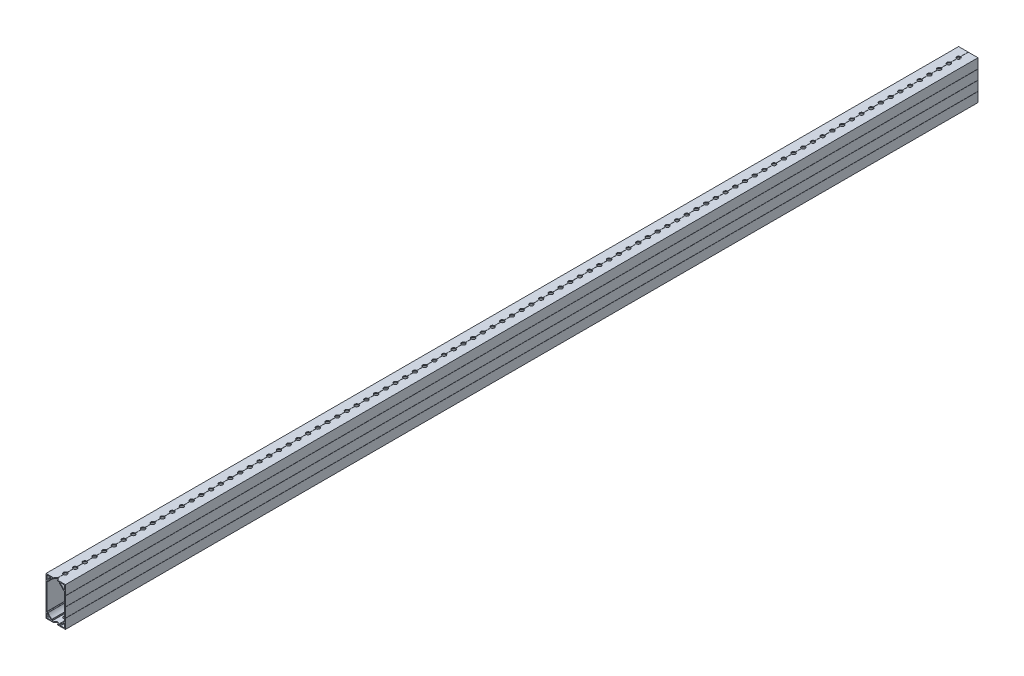
SolidWorks part; units mm, degrees
ref_plane "Front Plane" through (0, 0, 0) normal (0, 0, 1) x (1, 0, 0)
ref_plane "Top Plane" through (0, 0, 0) normal (0, 1, 0) x (1, 0, 0)
ref_plane "Right Plane" through (0, 0, 0) normal (1, 0, 0) x (0, 0, -1)
other "Configuration Table"
sketch "Sketch3" plane through (0, 0, 0) normal (0, 0, 1) x (1, 0, 0)
  line L0 (0, 12.7) -> (0, -12.7) construction
  line L1 (12.7, -25.4) -> (0.127, -25.4)
  line L2 (12.7, -12.827) -> (12.7, -25.4)
  line L3 (12.573, -12.7) -> (12.7, -12.827)
  line L4 (-10.9924, -24.384) -> (-6.5971, -24.384)
  line L5 (-11.684, -19.2971) -> (-11.684, -23.6924)
  line L6 (12.7, -12.573) -> (12.573, -12.7)
  line L7 (12.7, -0.127) -> (12.7, -12.573)
  line L10 (12.573, 0) -> (12.7, -0.127)
  line L11 (0.127, -25.4) -> (0, -25.273)
  line L14 (11.684, 0) -> (11.684, -17.5895)
  line L15 (11.684, -17.5895) -> (9.979, -17.5895)
  line L18 (4.8895, -22.679) -> (4.8895, -24.384)
  line L19 (11.684, -19.2971) -> (11.684, -23.6924)
  line L20 (10.9924, -24.384) -> (6.5971, -24.384)
  line L21 (13.97, 0) -> (-13.97, 0) construction
  line L37 (12.573, 0) -> (12.7, 0.127)
  line L46 (-4.8895, -24.384) -> (4.8895, -24.384)
  line L47 (-4.8895, -22.679) -> (-4.8895, -24.384)
  line L48 (-11.684, -17.5895) -> (-9.979, -17.5895)
  line L49 (-11.684, 0) -> (-11.684, -17.5895)
  line L57 (-0.127, 25.4) -> (-12.7, 25.4)
  line L58 (-12.7, 12.827) -> (-12.7, 25.4)
  line L59 (-12.573, 12.7) -> (-12.7, 12.827)
  line L60 (-12.7, 12.573) -> (-12.573, 12.7)
  line L61 (-12.7, 0.127) -> (-12.7, 12.573)
  line L62 (-12.573, 0) -> (-12.7, 0.127)
  line L63 (-0.127, 25.4) -> (0, 25.273)
  line L64 (-11.684, 0) -> (-11.684, 17.5895)
  line L65 (-11.684, 17.5895) -> (-9.979, 17.5895)
  line L66 (-4.8895, 22.679) -> (-4.8895, 24.384)
  line L67 (-4.8895, 24.384) -> (4.8895, 24.384)
  line L69 (10.9924, 24.384) -> (6.5971, 24.384)
  line L70 (11.684, 19.2971) -> (11.684, 23.6924)
  line L71 (4.8895, 22.679) -> (4.8895, 24.384)
  line L72 (11.684, 17.5895) -> (9.979, 17.5895)
  line L73 (11.684, 0) -> (11.684, 17.5895)
  line L74 (0.127, 25.4) -> (0, 25.273)
  line L76 (12.7, 0.127) -> (12.7, 12.573)
  line L77 (12.7, 12.573) -> (12.573, 12.7)
  line L78 (-11.684, 19.2971) -> (-11.684, 23.6924)
  line L79 (-10.9924, 24.384) -> (-6.5971, 24.384)
  line L80 (12.573, 12.7) -> (12.7, 12.827)
  line L81 (12.7, 12.827) -> (12.7, 25.4)
  line L82 (12.7, 25.4) -> (0.127, 25.4)
  line L96 (-0.127, -25.4) -> (0, -25.273)
  line L118 (-12.573, 0) -> (-12.7, -0.127)
  line L119 (-12.7, -0.127) -> (-12.7, -12.573)
  line L120 (-12.7, -12.573) -> (-12.573, -12.7)
  line L121 (-12.573, -12.7) -> (-12.7, -12.827)
  line L122 (-12.7, -12.827) -> (-12.7, -25.4)
  line L123 (-12.7, -25.4) -> (-0.127, -25.4)
  arc A0 (9.979, -17.5895) -> (4.8895, -22.679) centre (0, -12.7) cw
  arc A1 (6.5971, -24.384) -> (6.2412, -23.0994) centre (6.5971, -23.6924) cw
  arc A2 (10.3994, -18.9412) -> (6.2412, -23.0994) centre (0, -12.7) cw
  arc A3 (10.3994, -18.9412) -> (11.684, -19.2971) centre (10.9924, -19.2971) cw
  arc A4 (11.684, -23.6924) -> (10.9924, -24.384) centre (10.9924, -23.6924) cw
  arc A10 (-11.684, -23.6924) -> (-10.9924, -24.384) centre (-10.9924, -23.6924) ccw
  arc A11 (-10.3994, -18.9412) -> (-11.684, -19.2971) centre (-10.9924, -19.2971) ccw
  arc A12 (-10.3994, -18.9412) -> (-6.2412, -23.0994) centre (0, -12.7) ccw
  arc A14 (-6.5971, -24.384) -> (-6.2412, -23.0994) centre (-6.5971, -23.6924) ccw
  arc A24 (-9.979, 17.5895) -> (-4.8895, 22.679) centre (0, 12.7) cw
  arc A25 (-6.5971, 24.384) -> (-6.2412, 23.0994) centre (-6.5971, 23.6924) cw
  arc A30 (-10.3994, 18.9412) -> (-6.2412, 23.0994) centre (0, 12.7) cw
  arc A31 (-10.3994, 18.9412) -> (-11.684, 19.2971) centre (-10.9924, 19.2971) cw
  arc A32 (-11.684, 23.6924) -> (-10.9924, 24.384) centre (-10.9924, 23.6924) cw
  arc A33 (11.684, 23.6924) -> (10.9924, 24.384) centre (10.9924, 23.6924) ccw
  arc A34 (10.3994, 18.9412) -> (11.684, 19.2971) centre (10.9924, 19.2971) ccw
  arc A35 (10.3994, 18.9412) -> (6.2412, 23.0994) centre (0, 12.7) ccw
  arc A41 (6.5971, 24.384) -> (6.2412, 23.0994) centre (6.5971, 23.6924) ccw
  arc A42 (9.979, 17.5895) -> (4.8895, 22.679) centre (0, 12.7) ccw
  arc A46 (-9.979, -17.5895) -> (-4.8895, -22.679) centre (0, -12.7) ccw
  point P71 (0, -24.384)
  point P104 (-11.684, -8.7948)
  point P108 (11.684, -8.7948)
  point P130 (11.684, 8.7948)
  point P131 (-11.684, 8.7948)
  point P132 (0, 24.384)
  dimension "D4" = 0.6916
  dimension "D7" = 11.1125
  dimension "D14" = 12.1285
  dimension "D1" = 25.4
  dimension "D2" = 12.573
  dimension "D3" = 5.7785
  dimension "D5" = 12.7
  dimension "D6" = 4.8895
  dimension "D8" = 1.016
  dimension "D9" = 135
  dimension "D10" = 0.127
  dimension "D11" = 1.016
  dimension "D12" = 135
  dimension "D13" = 135
extrude "Boss-Extrude1" add sketch "Sketch3" along normal blind 1193.8 contours L48 A46 L47 L46 L18 A0 L15 L14 L73 L72 A42 L71 L67 L66 A24 L65 L64 L49 | A32 L78 A31 A30 A25 L79 | L69 A41 A35 A34 L70 A33 | L4 A14 A12 A11 L5 A10 | A4 L19 A3 A2 A1 L20 | L57 L58 L59 L60 L61 L62 L118 L119 L120 L121 L122 L123 L96 L11 L1 L2 L3 L6 L7 L10 L37 L76 L77 L80 L81 L82 L74 L63 region at (-9.5535, -22.2535, 0) region at (0, 0, 0) region at (9.5535, -22.2535, 0) region at (9.5535, 22.2535, 0) region at (-9.5535, 22.2535, 0)
sketch "Sketch2" plane through (25.4, 25.4, 0) normal (0, -1, 0) x (0, 0, 1)
  line L2 (1193.8, 25.4) -> (0, 25.4) construction
  line L3 (0, 12.7) -> (0, 25.273) construction
  circle A0 centre (12.7, 25.4) radius 2.54
  dimension "D1" = 5.08
  dimension "D2" = 12.7
extrude "Cut-Extrude1" cut sketch "Sketch2" along normal through all
pattern_linear "LPattern1" count 95 spacing 12.7 along (0, 0, 1) of "Cut-Extrude1"
fillet "Fillet1" radius 0.254 16 edges at (9.979, 17.5895, 596.9) (11.684, 17.5895, 596.9) (4.8895, 22.679, 596.9) (4.8895, 24.384, 596.9) (11.684, -17.5895, 596.9) (9.979, -17.5895, 596.9) (4.8895, -22.679, 596.9) (4.8895, -24.384, 596.9) (-4.8895, -22.679, 596.9) (-4.8895, -24.384, 596.9) (-9.979, -17.5895, 596.9) (-11.684, -17.5895, 596.9) (-4.8895, 24.384, 596.9) (-4.8895, 22.679, 596.9) (-11.684, 17.5895, 596.9) (-9.979, 17.5895, 596.9)
equation "\"Length\"= 47"
equation "\"D1@Boss-Extrude1\"=\"Length\""
